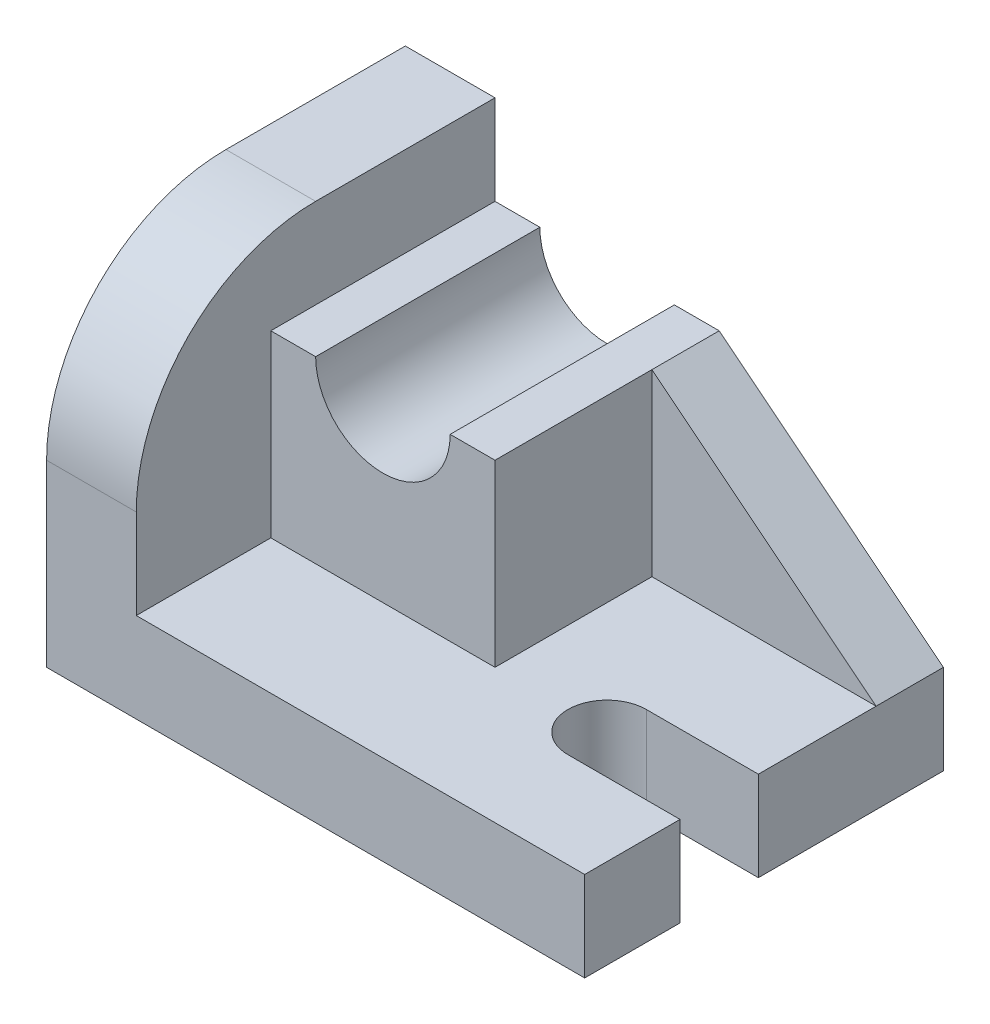
SolidWorks part; units mm, degrees
ref_plane "Front Plane" through (0, 0, 0) normal (0, 0, 1) x (1, 0, 0)
ref_plane "Top Plane" through (0, 0, 0) normal (0, 1, 0) x (1, 0, 0)
ref_plane "Right Plane" through (0, 0, 0) normal (1, 0, 0) x (0, 0, -1)
sketch "Sketch1" plane through (0, 0, 0) normal (0, 0, 1) x (1, 0, 0)
  line L0 (16, 64) -> (16, 16)
  line L1 (0, 0) -> (96, 0)
  line L4 (96, 0) -> (96, 16)
  line L7 (0, 64) -> (16, 64)
  line L14 (0, 64) -> (0, 0)
  line L15 (96, 16) -> (16, 16)
  line L16 (16, 48) -> (24, 48)
  line L17 (48, 48) -> (56, 48)
  line L18 (56, 48) -> (56, 16)
  line L19 (56, 48) -> (96, 16)
  arc A1 (24, 48) -> (48, 48) centre (36, 48) ccw
  dimension "D6" = 12
  dimension "D1" = 96
  dimension "D2" = 64
  dimension "D3" = 8
  dimension "D4" = 8
  dimension "D5" = 32
  dimension "D7" = 16
  dimension "D8" = 16
extrude "Boss-Extrude1" add sketch "Sketch1" along normal blind 64 contours L4 L15 L0 L7 L14 L1 region at (14.8462, 56, 0)
extrude "Boss-Extrude2" add sketch "Sketch1<3>" along normal blind 40 contours A1 L16 L0 L15 L18 L17 region at (36, 29.6589, 0)
sketch "Sketch1<3>" plane through (0, 0, 0) normal (0, 0, 1) x (1, 0, 0) same geometry as "Sketch1"
extrude "Boss-Extrude3" add sketch "Sketch1<4>" along normal blind 12 contours L19 L18 L15 region at (69.3333, 26.6667, 0)
sketch "Sketch1<4>" plane through (0, 0, 0) normal (0, 0, 1) x (1, 0, 0) same geometry as "Sketch1"
fillet "Fillet2" radius 32 1 edges at (8, 64, 64) type face fillet first side face at (8, 64, 32) second side face at (37.3333, 26.6667, 64)
sketch "Sketch2" plane through (0, 16, 0) normal (0, 1, 0) x (1, 0, 0)
  line L0 (96, -64) -> (16, -64) construction
  line L1 (76, -33.011) -> (96, -33.011)
  line L2 (96, -64) -> (96, -12) construction
  line L3 (76, -46.989) -> (96, -46.989)
  arc A0 (76, -33.011) -> (76, -46.989) centre (76, -40) ccw
  dimension "D1" = 24
  dimension "D2" = 20
extrude "Cut-Extrude1" cut sketch "Sketch2" against normal through all and the other way through all
